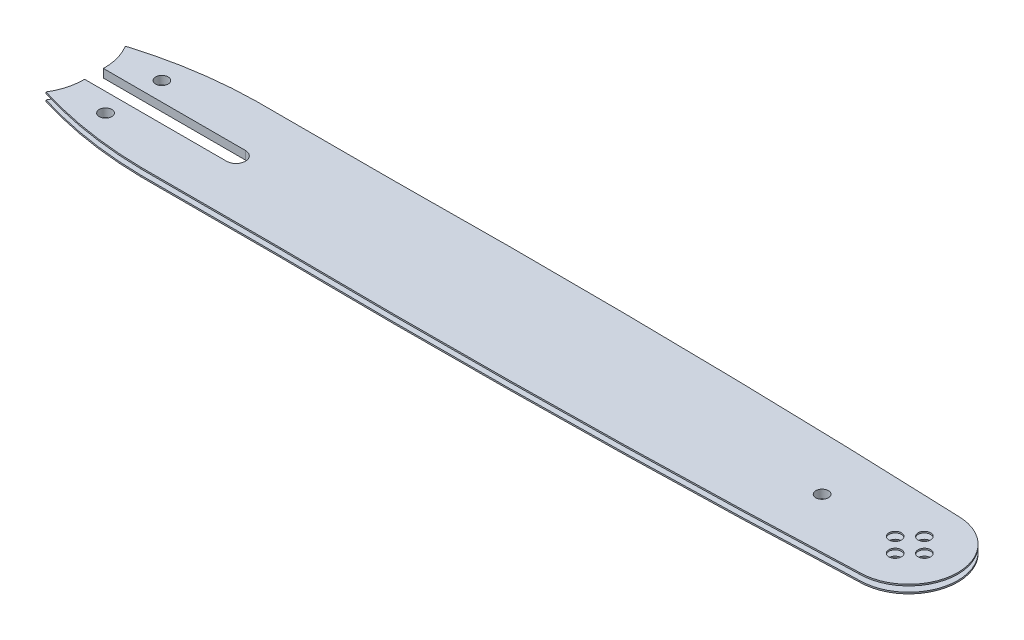
SolidWorks part; units mm, degrees
ref_plane "Front Plane" through (0, 0, 0) normal (0, 0, 1) x (1, 0, 0)
ref_plane "Top Plane" through (0, 0, 0) normal (0, 1, 0) x (1, 0, 0)
ref_plane "Right Plane" through (0, 0, 0) normal (1, 0, 0) x (0, 0, -1)
sketch "Sketch1" plane through (0, 0, 0) normal (0, 1, 0) x (1, 0, 0)
  line L0 (-222.0307, 0) -> (242.3216, 0) construction
  line L1 (-71.649, 27.5) -> (-138.4079, 27.5)
  line L5 (225.2989, 0) -> (202.2989, 0) construction
  line L6 (-71.649, 27.5) -> (-71.649, -26.8148) construction
  line L7 (-71.649, -27.5) -> (-138.4079, -27.5)
  line L8 (-120.4079, -4.5) -> (-188.4079, -4.5)
  line L9 (-120.4079, 4.5) -> (-188.4079, 4.5)
  line L12 (-188.4079, 4.5) -> (-191.7386, 4.5)
  line L13 (-169.4079, 31.7122) -> (-169.4079, -35.3307) construction
  arc A0 (201.7989, -23.5) -> (201.7989, 23.5) centre (201.7989, 0) ccw
  circle A1 centre (160.2989, 0) radius 3
  circle A2 centre (195.2989, 0) radius 3
  circle A3 centre (202.2989, 7) radius 3
  circle A4 centre (209.2989, 0) radius 3
  circle A5 centre (202.2989, -7) radius 3
  arc A6 (-120.4079, -4.5) -> (-120.4079, 4.5) centre (-120.4079, 0) ccw
  circle A7 centre (-169.4079, 13.5) radius 3
  arc A8 (-192.4079, 19) -> (-138.4079, 27.5) centre (-135.7586, -165.1102) cw
  arc A9 (-192.4079, 19) -> (-188.4079, 4.5) centre (-215.2249, 4.9039) cw
  circle A10 centre (-169.4079, -13.5) radius 3
  arc A11 (-192.4079, -19) -> (-188.4079, -4.5) centre (-215.2249, -4.9039) ccw
  arc A12 (-192.4079, -19) -> (-138.4079, -27.5) centre (-135.7586, 165.1102) ccw
  arc A13 (201.7989, 23.5) -> (-71.649, 27.5) centre (-8.9192, -5032.8906) ccw
  arc A14 (201.7989, -23.5) -> (-71.649, -27.5) centre (-8.9192, 5032.8906) cw
  point P23 (202.2989, 0)
  dimension "D2" = 23
  dimension "D5" = 4
  dimension "D7" = 4.5
  dimension "D10" = 6
  dimension "D11" = 6
  dimension "D12" = 6
  dimension "D6" = 23.5
  dimension "D1" = 65
  dimension "D3" = 23
  dimension "D4" = 7
  dimension "D8" = 9
  dimension "D9" = 19
  dimension "D13" = 68
extrude "Boss-Extrude2" add sketch "Sketch1" along normal blind 4 contours L9 A6 L8 A11 A12 L7 A14 A0 A13 L1 A8 A9
extrude "Cut-Extrude3" cut sketch "Sketch1<5>" along normal blind 54 contours A1 | A2 | A5 | A4 | A3 | A10
sketch "Sketch1<5>" plane through (0, 0, 0) normal (0, 1, 0) x (1, 0, 0) same geometry as "Sketch1"
extrude "Cut-Extrude4" cut sketch "Sketch1<6>" along normal blind 35 contours A7
sketch "Sketch1<6>" plane through (0, 0, 0) normal (0, 1, 0) x (1, 0, 0) same geometry as "Sketch1"
ref_plane "Plane1" through (0, 0, 0) normal (0, 0, 1) x (1, 0, 0)
ref_plane "Plane2" through (0, 2, 0) normal (0, 1, 0) x (1, 0, 0)
sketch "Sketch11" plane through (0, 2, 0) normal (0, 1, 0) x (1, 0, 0)
  line L11 (-71.649, 27.5) -> (-138.4079, 27.5) construction
  line L12 (-71.649, -27.5) -> (-138.4079, -27.5) construction
  line L13 (-138.3802, -23.5) -> (-71.6242, -23.5)
  line L14 (-71.6242, 23.5) -> (-138.3802, 23.5)
  line L15 (-138.3802, -23.5) -> (-71.6242, -23.5)
  line L16 (-71.6242, 23.5) -> (-138.3802, 23.5)
  line L17 (-71.649, 27.5) -> (-138.4079, 27.5)
  line L18 (-71.649, -27.5) -> (-138.4079, -27.5)
  arc A22 (201.7989, -23.5) -> (201.7989, 23.5) centre (201.7989, 0) ccw construction
  arc A23 (-188.4079, 4.5) -> (-192.4079, 19) centre (-215.2249, 4.9039) ccw construction
  arc A24 (-138.4079, 27.5) -> (-192.4079, 19) centre (-135.7586, -165.1102) ccw construction
  arc A25 (201.7989, 23.5) -> (-71.649, 27.5) centre (-8.9192, -5032.8906) ccw construction
  arc A26 (-71.649, -27.5) -> (201.7989, -23.5) centre (-8.9192, 5032.8906) ccw construction
  arc A27 (201.7195, -19.4998) -> (201.7195, 19.4998) centre (201.7989, 0) ccw
  arc A28 (201.7195, 19.4998) -> (-71.6242, 23.5) centre (-8.9192, -5032.8906) ccw
  arc A29 (-71.6242, -23.5) -> (201.7195, -19.4998) centre (-8.9192, 5032.8906) ccw
  arc A30 (-138.3802, 23.5) -> (-191.2316, 15.1769) centre (-135.7586, -165.1102) ccw
  arc A31 (-191.2316, -15.1769) -> (-138.3802, -23.5) centre (-135.7586, 165.1102) ccw
  arc A33 (183.6606, 20.2204) -> (-71.6242, 23.5) centre (-8.9192, -5032.8906) ccw
  arc A34 (-71.6242, -23.5) -> (183.6606, -20.2204) centre (-8.9192, 5032.8906) ccw
  arc A35 (-138.3802, 23.5) -> (-190.5391, 15.3885) centre (-135.7586, -165.1102) ccw
  arc A36 (-190.5391, -15.3885) -> (-138.3802, -23.5) centre (-135.7586, 165.1102) ccw
  arc A37 (-192.4079, -19) -> (-188.4079, -4.5) centre (-215.2249, -4.9039) ccw construction
  arc A38 (-192.4079, -19) -> (-138.4079, -27.5) centre (-135.7586, 165.1102) ccw construction
  arc A39 (201.7989, -23.5) -> (201.7989, 23.5) centre (201.7989, 0) ccw
  arc A40 (-190.5391, 15.3885) -> (-192.4079, 19) centre (-215.2249, 4.9039) ccw
  arc A41 (-138.4079, 27.5) -> (-192.4079, 19) centre (-135.7586, -165.1102) ccw
  arc A42 (201.7989, 23.5) -> (-71.649, 27.5) centre (-8.9192, -5032.8906) ccw
  arc A43 (-71.649, -27.5) -> (201.7989, -23.5) centre (-8.9192, 5032.8906) ccw
  arc A44 (-192.4079, -19) -> (-190.5391, -15.3885) centre (-215.2249, -4.9039) ccw
  arc A45 (-192.4079, -19) -> (-138.4079, -27.5) centre (-135.7586, 165.1102) ccw
  arc A46 (183.6606, 20.2204) -> (183.6606, -20.2204) centre (202.2989, 0) ccw
  dimension "D2" = 55
  dimension "D1" = 4
extrude "Cut-Extrude6" cut sketch "Sketch11" against normal blind 1.3 and the other way blind 1.3
